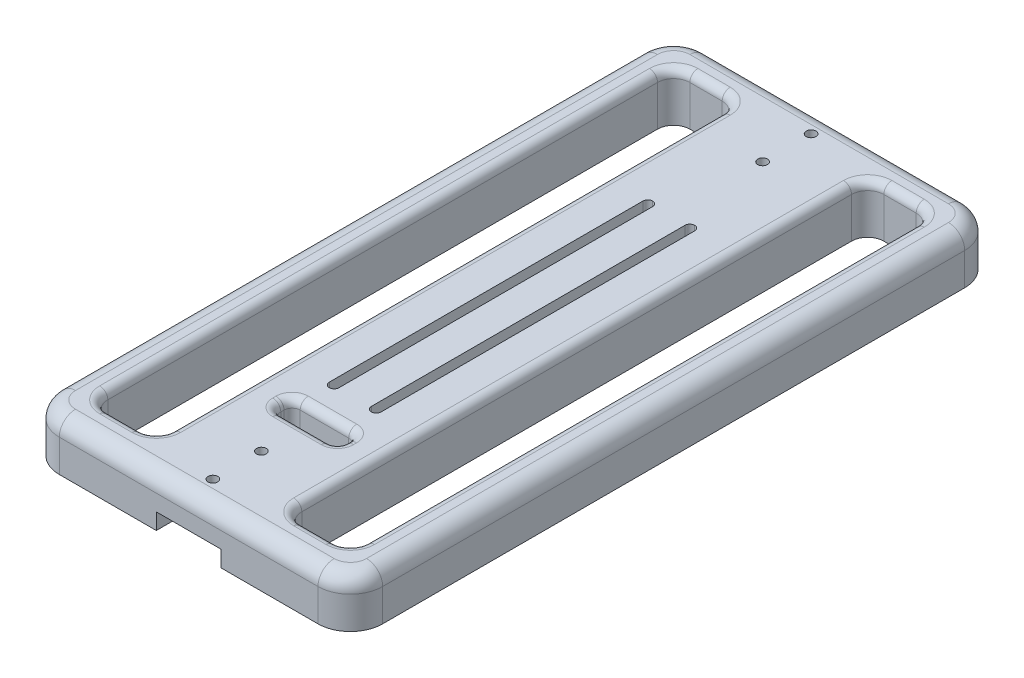
SolidWorks part; units mm, degrees
ref_plane "Front Plane" through (0, 0, 0) normal (0, 0, 1) x (1, 0, 0)
ref_plane "Top Plane" through (0, 0, 0) normal (0, 1, 0) x (1, 0, 0)
ref_plane "Right Plane" through (0, 0, 0) normal (1, 0, 0) x (0, 0, -1)
sketch "Sketch1" plane through (0, 0, 0) normal (0, 1, 0) x (1, 0, 0)
  line L1 (-50, 100) -> (50, 100)
  line L2 (-50, 100) -> (-50, -100)
  line L3 (-50, -100) -> (50, -100)
  line L4 (50, 100) -> (50, -100)
  line L5 (-50, 100) -> (50, -100) construction
  line L6 (-50, -100) -> (50, 100) construction
  point P0 (0, 0)
  dimension "D1" = 200
  dimension "D2" = 100
extrude "Boss-Extrude1" add sketch "Sketch1" along normal blind 15
sketch "Sketch4" plane through (0, 0, 0) normal (0, -1, 0) x (1, 0, 0)
  line L0 (-50, 100) -> (50, 100) construction
  line L1 (-10, 100) -> (10, 100)
  line L2 (-10, 100) -> (-10, 70)
  line L3 (-10, 70) -> (10, 70)
  line L4 (10, 100) -> (10, 70)
  line L5 (50, -100) -> (-50, -100) construction
  line L6 (-10, -100) -> (10, -100)
  line L7 (-10, -100) -> (-10, -70)
  line L8 (-10, -70) -> (10, -70)
  line L9 (10, -100) -> (10, -70)
  line L10 (50, 100) -> (50, -100) construction
  line L11 (-50, -100) -> (-50, 100) construction
  line L13 (-10, 52) -> (-3, 52)
  line L14 (-10, 52) -> (-10, -52)
  line L15 (-10, -52) -> (-3, -52)
  line L16 (-3, 52) -> (-3, -52)
  line L17 (10, 52) -> (3, 52)
  line L18 (10, 52) -> (10, -52)
  line L19 (10, -52) -> (3, -52)
  line L20 (3, 52) -> (3, -52)
  dimension "D1" = 20
  dimension "D2" = 30
  dimension "D3" = 20
  dimension "D4" = 30
  dimension "D5" = 40
  dimension "D6" = 40
  dimension "D7" = 18
  dimension "D8" = 18
  dimension "D9" = 18
  dimension "D10" = 18
  dimension "D11" = 7
  dimension "D12" = 7
  dimension "D13" = 40
  dimension "D14" = 40
extrude "Cut-Extrude2" cut sketch "Sketch4" against normal blind 5
fillet "Fillet3" radius 10 4 edges at (50, 7.5, -100) (-50, 7.5, -100) (-50, 7.5, 100) (50, 7.5, 100)
fillet "Fillet4" radius 5 8 edges at (-47.0711, 15, 97.0711) (-50, 15, 0) (-47.0711, 15, -97.0711) (0, 15, -100) (47.0711, 15, -97.0711) (50, 15, 0) (47.0711, 15, 97.0711) (0, 15, 100)
sketch "Sketch8" plane through (0, 0, 0) normal (0, -1, 0) x (1, 0, 0)
  line L0 (10, -52) -> (10, 52) construction
  line L1 (20, 90) -> (40, 90)
  line L2 (20, 90) -> (20, -90)
  line L3 (20, -90) -> (40, -90)
  line L4 (40, 90) -> (40, -90)
  line L5 (-40, 90) -> (-20, 90)
  line L6 (-40, 90) -> (-40, -90)
  line L7 (-40, -90) -> (-20, -90)
  line L8 (-20, 90) -> (-20, -90)
  line L9 (-8, 50) -> (-5, 50)
  line L10 (-8, 50) -> (-8, -50)
  line L11 (-8, -50) -> (-5, -50)
  line L12 (-5, 50) -> (-5, -50)
  line L13 (5, 50) -> (8, 50)
  line L14 (5, 50) -> (5, -50)
  line L15 (5, -50) -> (8, -50)
  line L16 (8, 50) -> (8, -50)
  line L17 (-10, 64) -> (10, 64)
  line L18 (-10, 64) -> (-10, 58)
  line L19 (-10, 58) -> (10, 58)
  line L20 (10, 64) -> (10, 58)
  line L21 (-3, -52) -> (-3, 52) construction
  line L22 (-3, 52) -> (-10, 52) construction
  line L23 (10, 52) -> (3, 52) construction
  line L24 (3, -52) -> (10, -52) construction
  line L25 (-10, -52) -> (-3, -52) construction
  line L26 (50, 90) -> (50, -90) construction
  line L27 (10, 100) -> (40, 100) construction
  line L28 (40, -100) -> (10, -100) construction
  line L29 (-40, 100) -> (-10, 100) construction
  line L31 (-50, -90) -> (-50, 90) construction
  line L32 (-10, -100) -> (-40, -100) construction
  line L36 (-3, 52) -> (-10, 52) construction
  line L38 (-10, 100) -> (-10, 70) construction
  dimension "D1" = 3
  dimension "D2" = 3
  dimension "D3" = 2
  dimension "D4" = 2
  dimension "D5" = 2
  dimension "D6" = 2
  dimension "D7" = 2
  dimension "D8" = 2
  dimension "D9" = 20
  dimension "D10" = 10
  dimension "D11" = 10
  dimension "D12" = 10
  dimension "D13" = 10
  dimension "D14" = 20
  dimension "D15" = 10
  dimension "D16" = 10
  dimension "D17" = 6
  dimension "D18" = 6
  dimension "D19" = 20
extrude "Cut-Extrude3" cut sketch "Sketch8" against normal blind 15
fillet "Fillet5" radius 5 8 edges at (-40, 7.5, -90) (-20, 7.5, -90) (20, 7.5, -90) (40, 7.5, -90) (-20, 7.5, 90) (-40, 7.5, 90) (20, 7.5, 90) (40, 7.5, 90)
fillet "Fillet8" radius 2.5 4 edges at (10, 7.5, 64) (10, 7.5, 58) (-10, 7.5, 58) (-10, 7.5, 64)
fillet "Fillet7" radius 2.5 24 edges at (21.4645, 15, 88.5355) (30, 15, 90) (38.5355, 15, 88.5355) (40, 15, 0) (38.5355, 15, -88.5355) (30, 15, -90) (21.4645, 15, -88.5355) (-38.5355, 15, 88.5355) (-30, 15, 90) (-21.4645, 15, 88.5355) (-20, 15, 0) (-21.4645, 15, -88.5355) (-30, 15, -90) (-38.5355, 15, -88.5355) (20, 15, 0) (-40, 15, 0) (9.2678, 15, 63.2678) (10, 15, 61) (9.2678, 15, 58.7322) (0, 15, 58) (-9.2678, 15, 58.7322) (-10, 15, 61) (-9.2678, 15, 63.2678) (0, 15, 64)
fillet "Fillet10" radius 1.5 8 edges at (8, 10, -50) (5, 10, -50) (-5, 10, -50) (-8, 10, -50) (5, 10, 50) (8, 10, 50) (-8, 10, 50) (-5, 10, 50)
hole_wizard "Ø3.0mm Dowel Hole1" positions "Sketch11" profile "Sketch10" hole size "Ø3.0" standard "ANSI Metric" end condition through all
sketch "Sketch11" plane through (0, 5, 0) normal (0, -1, 0) x (-1, 0, 0)
  line L0 (-10, 70) -> (10, 70) construction
  line L1 (10, 100) -> (-10, 100) construction
  line L2 (-10, 100) -> (-10, 70) construction
  line L3 (-10, 100) -> (-10, 70) construction
  point P0 (0, 77.5)
  point P2 (0, 92.5)
  dimension "D1" = 7.5
  dimension "D2" = 7.5
  dimension "D3" = 10
  dimension "D4" = 10
sketch "Sketch10" plane through (0, 5, -77.5) normal (1, 0, 0) x (0, 0, -1)
  line L0 (0, 0) -> (0, 10)
  line L1 (0, 10) -> (1.5, 10)
  line L2 (1.5, 10) -> (1.5, 0)
  line L5 (1.5, 0) -> (0, 0)
  line L11 (0, -6.35) -> (0, 107.95) construction
  dimension "Thru Hole Dia." = 3
  dimension "Thru Hole Depth" = 10
hole_wizard "Ø3.0mm Dowel Hole2" positions "Sketch12" profile "Sketch13" hole size "Ø3.0" standard "ANSI Metric" end condition through all
sketch "Sketch12" plane through (0, 5, 0) normal (0, -1, 0) x (-1, 0, 0)
  line L0 (-10, -100) -> (10, -100) construction
  line L1 (10, -70) -> (-10, -70) construction
  line L2 (-10, -70) -> (-10, -100) construction
  line L3 (-10, -70) -> (-10, -100) construction
  point P0 (0, -92.5)
  point P2 (0, -77.5)
  dimension "D1" = 7.5
  dimension "D2" = 7.5
  dimension "D3" = 10
  dimension "D4" = 10
sketch "Sketch13" plane through (0, 5, 92.5) normal (1, 0, 0) x (0, 0, -1)
  line L0 (0, 0) -> (0, 10)
  line L1 (0, 10) -> (1.5, 10)
  line L2 (1.5, 10) -> (1.5, 0)
  line L5 (1.5, 0) -> (0, 0)
  line L11 (0, -6.35) -> (0, 107.95) construction
  dimension "Thru Hole Dia." = 3
  dimension "Thru Hole Depth" = 10
